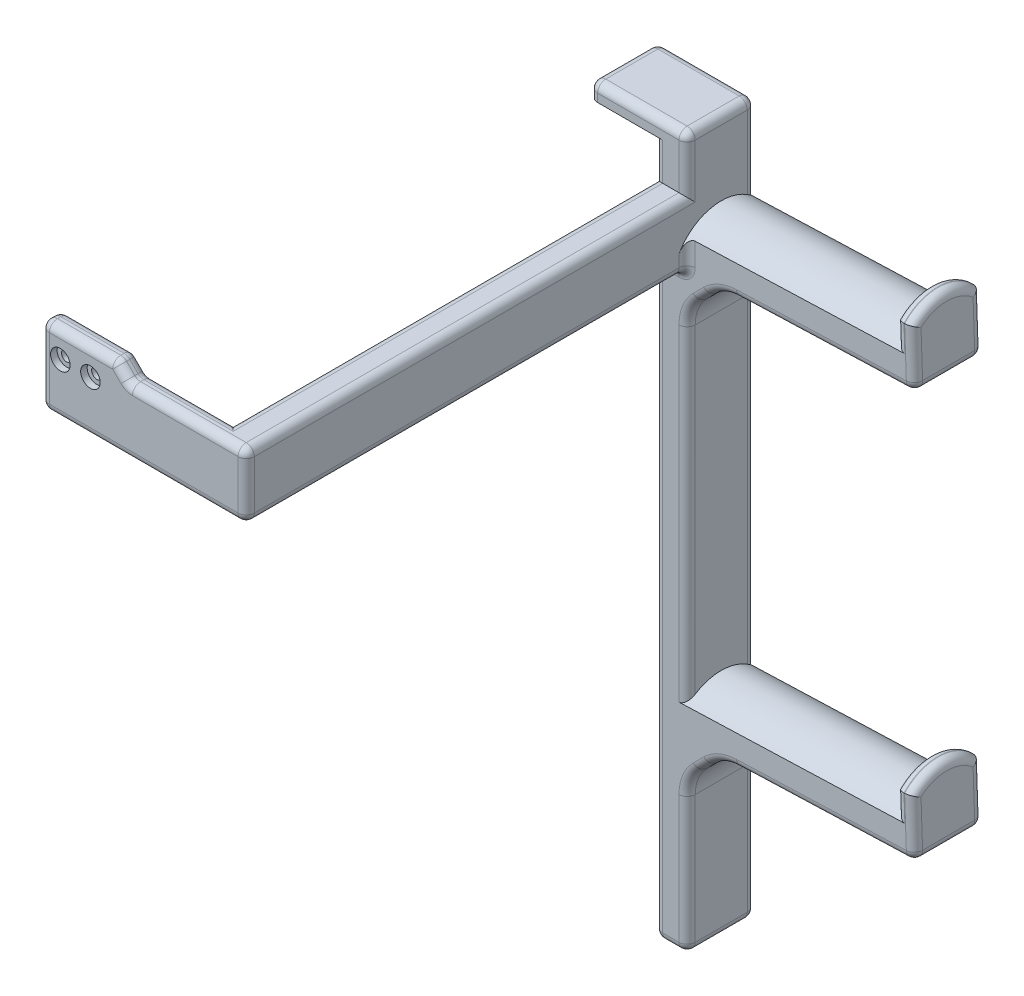
SolidWorks part; units mm, degrees
ref_plane "Front Plane" through (0, 0, 0) normal (0, 0, 1) x (1, 0, 0)
ref_plane "Top Plane" through (0, 0, 0) normal (0, 1, 0) x (1, 0, 0)
ref_plane "Right Plane" through (0, 0, 0) normal (1, 0, 0) x (0, 0, -1)
sketch "Sketch2" plane through (0, 0, 0) normal (0, 0, 1) x (1, 0, 0)
  line L0 (-4.625, 0) -> (4.625, 0) construction
  line L1 (-10.5, -16) -> (10.5, -16)
  line L2 (-10.5, -16) -> (-10.5, 8)
  line L3 (-10.5, 8) -> (10.5, 8)
  line L4 (10.5, -16) -> (10.5, 8)
  line L5 (0, 8) -> (0, -16) construction
  circle A0 centre (-4.625, 0) radius 1.625
  circle A1 centre (4.625, 0) radius 1.625
  point P0 (0, 0)
  point P8 (0, 0)
  dimension "D3" = 3.25
  dimension "D1" = 21
  dimension "D2" = 9.25
  dimension "D4" = 8
  dimension "D5" = 16
extrude "Boss-Extrude1" add sketch "Sketch2" against normal blind 6
sketch "Sketch4" plane through (0, 0, 0) normal (0, 0, 1) x (1, 0, 0)
  line L4 (42.5, 4) -> (42.5, -16)
  line L7 (42.5, 4) -> (10.5, 4)
  line L8 (10.5, -16) -> (10.5, 8) construction
  line L9 (10.5, 4) -> (10.5, -16)
  line L10 (10.5, -16) -> (42.5, -16)
  dimension "D1" = 20
  dimension "D4" = 42.5
extrude "Boss-Extrude3" add sketch "Sketch4" against normal up to surface (6 mm away) up to face at (6.25, 0, -6)
sketch "Sketch5" plane through (42.5, 0, 0) normal (1, 0, 0) x (0, 0, -1)
  line L0 (6, -16) -> (6, 4) construction
  line L1 (0, 4) -> (146, 4)
  line L2 (0, 4) -> (0, -16)
  line L3 (0, -16) -> (146, -16)
  line L4 (146, 4) -> (146, -16) construction
  line L5 (146, 4) -> (156.5, 4)
  line L6 (156.5, 4) -> (156.5, -16)
  line L7 (156.5, -16) -> (146, -16)
  dimension "D1" = 140
  dimension "D2" = 10.5
extrude "Boss-Extrude4" add sketch "Sketch5" along normal blind 10
sketch "Sketch9" plane through (0, 4, 0) normal (0, 1, 0) x (1, 0, 0)
  line L0 (42.5, 156.5) -> (42.5, 6) construction
  line L1 (52.5, 156.5) -> (42.5, 156.5)
  line L2 (52.5, 156.5) -> (52.5, 135.5)
  line L3 (52.5, 135.5) -> (42.5, 135.5)
  line L4 (42.5, 156.5) -> (42.5, 135.5)
extrude "Boss-Extrude7" add sketch "Sketch9" along normal blind 11.5 and the other way blind 202
ref_plane "Plane11" through (51.878, 1.8116, 0) normal (0.9994, 0.0349, 0) x (0, 0, -1)
sketch "Sketch7" plane through (51.9695, -0.8078, 0) normal (0.9994, 0.0349, 0) x (0, 0, -1)
  line L1 (156.5, -15.2014) -> (135.5, -15.2014)
  line L2 (156.5, -15.2014) -> (156.5, -5.7014)
  line L4 (135.5, -15.2014) -> (135.5, -5.7014)
  arc A0 (135.5, -5.7014) -> (156.5, -5.7014) centre (146, -16.2014) cw
  dimension "D1" = 21
  dimension "D2" = 9.5
extrude "Boss-Extrude9" add sketch "Sketch7" along normal blind 70
sketch "Sketch8" plane through (121.9117, 2.068, 0) normal (0.9994, 0.0349, 0) x (0, 0, -1)
  line L0 (156.5, -15.6345) -> (135.5, -15.6345)
  line L1 (135.5, -15.6345) -> (135.5, 1.8655)
  line L2 (156.5, -15.6345) -> (156.5, 1.8655)
  arc A0 (135.5, 1.8655) -> (156.5, 1.8655) centre (146, -8.6345) cw
  dimension "D1" = 17.5
extrude "Boss-Extrude6" add sketch "Sketch8" against normal blind 5.2
pattern_linear "LPattern1" count 2 spacing 125 along (0, -1, 0) of "Boss-Extrude9", "Boss-Extrude6"
sketch "Sketch10" plane through (0, 15.5, 0) normal (0, 1, 0) x (1, 0, 0)
  line L0 (42.5, 135.5) -> (42.5, 156.5) construction
  line L1 (52.5, 156.5) -> (22.5, 156.5)
  line L2 (52.5, 156.5) -> (52.5, 135.5)
  line L3 (52.5, 135.5) -> (22.5, 135.5)
  line L4 (22.5, 156.5) -> (22.5, 135.5)
  dimension "D1" = 20
extrude "Boss-Extrude8" add sketch "Sketch10" along normal blind 5
chamfer "Chamfer1" distance 6 angle 45 1 edges at (10.5, 4, -3)
chamfer "Chamfer2" distance 10 angle 45 2 edges at (52.5, -16, -146) (52.5, -141, -146)
fillet "Fillet2" radius 12.5 4 edges at (52.5, -26, -146) (62.8618, -15.6382, -146) (52.5, -151, -146) (62.8618, -140.6382, -146)
fillet "Fillet1" radius 2.5 71 edges at (52.5, -81.3359, -135.5) (52.5, -81.3359, -156.5) (52.5, -127.1423, -146) (95.12, -139.5117, -156.5) (95.12, -139.5117, -135.5) (122.152, -129.8124, -156.5) (122.152, -129.8124, -135.5) (122.4574, -138.557, -146) (-10.5, -4, -6) (121.6948, -116.7211, -146) (116.7894, -125.2467, -156.5) (116.7894, -125.2467, -135.5) (116.498, -116.9026, -146) (22.5, 18, -156.5) (22.5, 18, -135.5) (52.5, 20.5, -146) (37.5, 20.5, -156.5) (22.5, 20.5, -146) (37.5, 20.5, -135.5) (16.5, 4, -3) (14.5, 6, 0) (16, -16, -6) (12.5, 8, -3) (14.5, 6, -6) (57.7706, -145.7294, -135.5) (57.7706, -145.7294, -156.5) (57.7706, -20.7294, -135.5) (57.7706, -20.7294, -156.5) (53.4515, -151.3941, -135.5) (53.4515, -151.3941, -156.5) (63.2346, -141.4954, -156.5) (63.2346, -141.4954, -135.5) (53.4515, -26.3941, -135.5) (53.4515, -26.3941, -156.5) (63.2346, -16.4954, -156.5) (63.2346, -16.4954, -135.5) (34.5, 4, 0) (29.5, 4, -6) (42.5, -16, -70.75) (42.5, -91.25, -156.5) (52.5, -6, 0) (52.5, -16, -67.75) (52.5, -177.0888, -156.5) (21, -16, 0) (52.5, 4, -67.75) (42.5, 4, -70.75) (-10.5, -4, 0) (52.5, -198, -146) (42.5, -107, -135.5) (42.5, -198, -146) (52.5, -177.0888, -135.5) (47.5, -16, -135.5) (47.5, -198, -135.5) (47.5, -198, -156.5) (1, 8, 0) (52.5, 12.25, -135.5) (42.5, 9.75, -135.5) (52.5, 7.0029, -156.5) (52.5, -11.2471, -135.5) (-10.5, -16, -3) (95.12, -14.5117, -156.5) (95.12, -14.5117, -135.5) (122.152, -4.8124, -156.5) (-10.5, 8, -3) (122.152, -4.8124, -135.5) (122.4574, -13.557, -146) (1, 8, -6) (121.6948, 8.2789, -146) (116.7894, -0.2467, -156.5) (116.7894, -0.2467, -135.5) (116.498, 8.0974, -146)
sketch "Sketch12" plane through (0, 0, 0) normal (0, 0, 1) x (1, 0, 0)
  circle A0 centre (-4.625, 0) radius 3
  circle A1 centre (4.625, 0) radius 3
  dimension "D1" = 6
extrude "Cut-Extrude2" cut sketch "Sketch12" against normal blind 2
